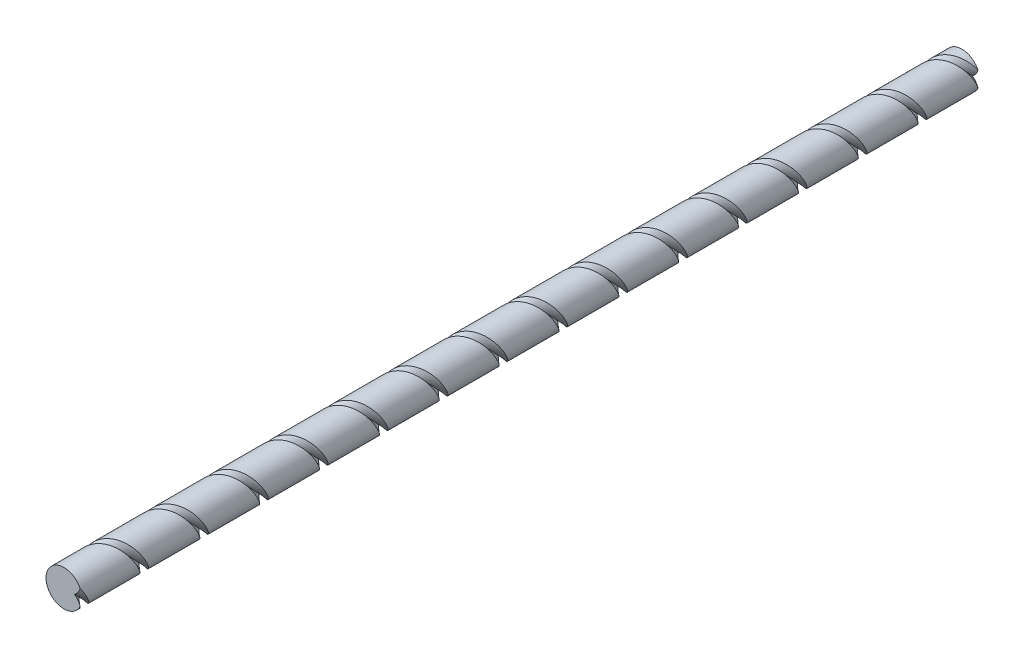
SolidWorks part; units mm, degrees
ref_plane "Alzado" through (0, 0, 0) normal (0, 0, 1) x (1, 0, 0)
ref_plane "Planta" through (0, 0, 0) normal (0, 1, 0) x (1, 0, 0)
ref_plane "Vista lateral" through (0, 0, 0) normal (1, 0, 0) x (0, 0, -1)
sketch "Croquis1" plane through (0, 0, 0) normal (0, 0, 1) x (1, 0, 0)
  circle A0 centre (0, 0) radius 6
  dimension "D1" = 12
extrude "Saliente-Extruir1" add sketch "Croquis1" along normal blind 300
sketch "Croquis2" plane through (0, 0, 300) normal (0, 0, 1) x (1, 0, 0)
  circle A1 centre (0, 0) radius 6
  circle A2 centre (0, 0) radius 6
  dimension "D1" = 0
curve "Hélice/Espiral1" pitch 20 height 1200 turns 60
sketch "Croquis4" plane through (0, 0, 0) normal (0, 1, 0) x (1, 0, 0)
  line L4 (6, -300) -> (6, -298.5566)
  line L5 (6, -300) -> (6, 0) construction
  line L6 (6, -298.5566) -> (3.5, -300)
  line L7 (-6, -300) -> (6, -300) construction
  line L8 (3.5, -300) -> (6, -301.4434)
  line L9 (6, -301.4434) -> (6, -300)
  dimension "D1" = 60
  dimension "D2" = 60
  dimension "D3" = 2.5
sweep "Cortar-Barrer2" cut profiles "Croquis4" path "Hélice/Espiral1"
